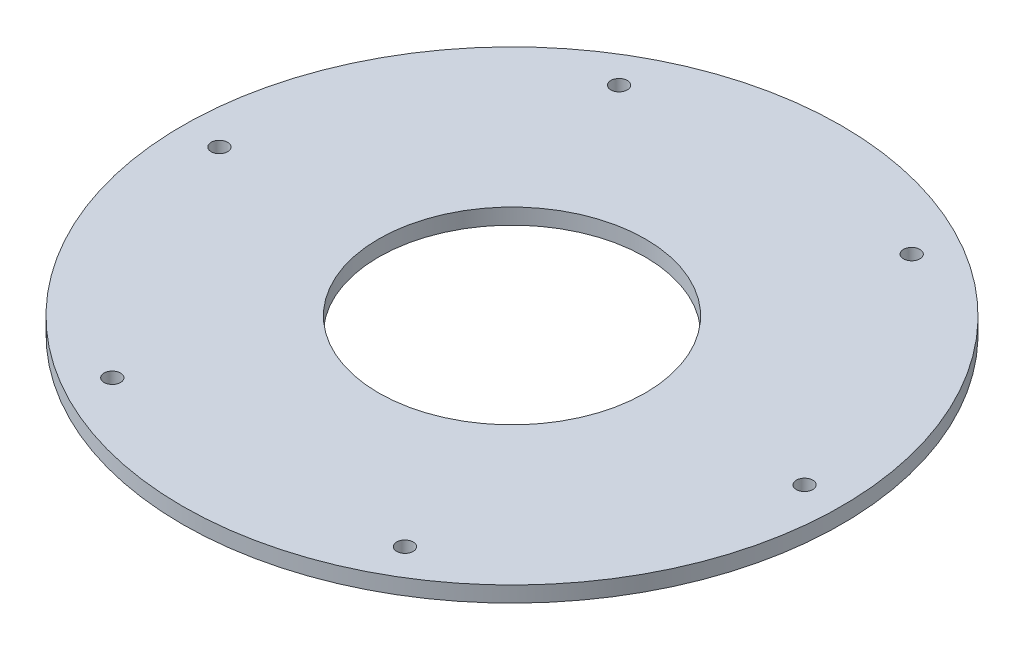
SolidWorks part; units mm, degrees
material "1060 Alloy"
ref_plane "Front Plane" through (0, 0, 0) normal (0, 0, 1) x (1, 0, 0)
ref_plane "Top Plane" through (0, 0, 0) normal (0, 1, 0) x (1, 0, 0)
ref_plane "Right Plane" through (0, 0, 0) normal (1, 0, 0) x (0, 0, -1)
sketch "Sketch2" plane through (0, 0, 0) normal (0, 1, 0) x (1, 0, 0)
  line L0 (-37.2875, 0) -> (0, 0) construction
  circle A0 centre (0, 0) radius 42
  circle A1 centre (0, 0) radius 37.2875 construction
  circle A2 centre (-37.2875, 0) radius 1.05
  circle A3 centre (-18.6438, 32.2919) radius 1.05
  circle A4 centre (18.6438, 32.2919) radius 1.05
  circle A5 centre (37.2875, 0) radius 1.05
  circle A6 centre (18.6438, -32.2919) radius 1.05
  circle A7 centre (-18.6437, -32.2919) radius 1.05
  circle A8 centre (0, 0) radius 17
  point P6 (0, 0)
  point P18 (0, 0)
  dimension "D1" = 2.1
  dimension "D3" = 74.575
  dimension "D4" = 84
  dimension "D5" = 34
  dimension "D2" = 6
extrude "Boss-Extrude1" add sketch "Sketch2" along normal blind 2
equation "\"D5@Sketch2\" = \"Rotor_ID\""
equation "\"Stator_OD\"= 68'No Tolerance given"
equation "\"A\"=18.34"
equation "\"Rotor_ID\"= 34'No Tolerance Given"
equation "\"back_bearing_Thickness\"= 8'randomish, thinnest off mcmaster"
equation "\"back_bearing_OD\"= 25'currently non-sense"
equation "\"Stator_Gap\"= 0.0375'+- 0.0125 (From 1.3.3.1 Kollmorgen manual)"
equation "\"Back_mount_hole\"= 1.75'To be tapped to M2 (USE LOCKTITE)"
equation "\"facePlate_Mount_Hole\"= 5.75'To be tapped to M6"
equation "\"back_bearing_ID\"= 15'Random number"
equation "\"final_shaftD\"= 8'NEMA 23 shaft diameter. Should fit with harmonic?"
equation "\"final_shaftL\"= 50'random length. Idk"
equation "\"back_bearing_IDOD\"= 20'Random number, OD of the inner bearing ring"
equation "\"rotor_shaftD\"= \"Rotor_ID\" - (0.0185)*2'+-0.0065 (from manual)"
equation "\"D4@Sketch2\"=\"Stator_OD\"+16"
equation "\"D3@Sketch2\"=\"Stator_OD\"+\"Stator_Gap\"*2+6.5"
equation "\"front_bearing_ID\"= 12'random"
equation "\"front_bearing_OD\"= 20'random"
equation "\"front_bearing_IDOD\"= 14'random"
equation "\"front_bearing_Thickness\"= 5'randomish, thinnest off mcmaster"
equation "\"rotor_thickness\"= 2.4'measured off CAD"
equation "\"rotor_height\"= 14.8'measured off CAD"
